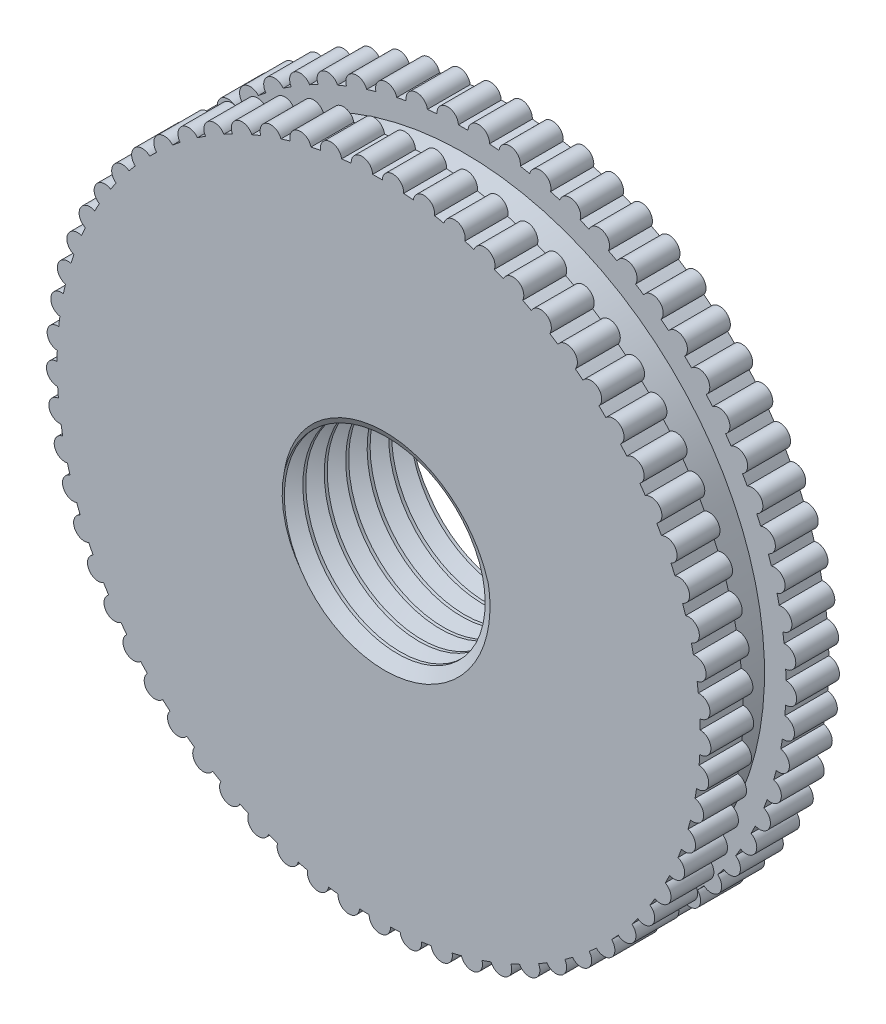
SolidWorks part; units mm, degrees
ref_plane "Front" through (0, 0, 0) normal (0, 0, 1) x (1, 0, 0)
ref_plane "Top" through (0, 0, 0) normal (0, 1, 0) x (1, 0, 0)
ref_plane "Right" through (0, 0, 0) normal (1, 0, 0) x (0, 0, -1)
sketch "Sketch1" plane through (0, 0, 0) normal (0, 0, 1) x (1, 0, 0)
  circle A0 centre (0, 0) radius 2.25
  circle A1 centre (0, 0) radius 7.5
  dimension "D1" = 4.5
  dimension "D2" = 15
extrude "Boss-Extrude1" add sketch "Sketch1" along normal blind 3
sketch "Sketch2" plane through (0, 0, 3) normal (0, 0, 1) x (1, 0, 0)
  circle A0 centre (0, 0) radius 2.25 construction
  circle A1 centre (0, 0) radius 2.25
curve "Helix/Spiral1" pitch 0.5 height 4.25 radius 2.25 centre (0, 0, 3) axis (0, 0, -1) start towards (1, 0, 0)
ref_plane "Plane1" through (2.25, 0, 3) normal (0, -0.9994, -0.0353) x (-1, 0, 0)
sketch "Sketch3" plane through (2.25, 0, 3) normal (0, -0.9994, -0.0353) x (-1, 0, 0)
  line L1 (-0.3732, 0.0174) -> (0.0425, -0.2226)
  line L2 (0.0425, -0.2226) -> (0.0425, 0.2574)
  line L3 (0.0425, 0.2574) -> (-0.3732, 0.0174)
  circle A0 centre (-0.096, 0.0174) radius 0.1386 construction
  point P1 (-0.096, 0.0174)
  dimension "D1" = 0.48
sweep "Cut-Sweep1" cut profiles "Sketch3" path "Helix/Spiral1" align with end faces yes
ref_plane "Plane2" through (0, 0, 0) normal (0, 0, -1) x (-1, 0, 0)
ref_plane "Plane3" through (0, 0, 1.5) normal (0, 0, -1) x (-1, 0, 0)
sketch "Sketch5" plane through (0, 0, 1.5) normal (0, 0, -1) x (-1, 0, 0)
  circle A0 centre (0, 0) radius 7.5 construction
  circle A1 centre (0, 0) radius 7.5
  circle A4 centre (0, 0) radius 7
  dimension "D1" = 0.5
extrude "Cut-Extrude1" cut sketch "Sketch5" against normal blind 0.5 and the other way blind 0.5
sketch "Sketch6" plane through (0, 0, 0) normal (0, 0, -1) x (-1, 0, 0)
  circle A0 centre (7.3977, 1.2348) radius 0.25
  circle A1 centre (0, 0) radius 7.5 construction
  circle A2 centre (7.4823, 0.5151) radius 0.25
  circle A3 centre (7.4971, -0.2095) radius 0.25
  circle A4 centre (7.4419, -0.9321) radius 0.25
  circle A5 centre (7.3172, -1.646) radius 0.25
  circle A6 centre (7.1241, -2.3445) radius 0.25
  circle A7 centre (6.8646, -3.0211) radius 0.25
  circle A8 centre (6.541, -3.6695) radius 0.25
  circle A9 centre (6.1563, -4.2837) radius 0.25
  circle A10 centre (5.7141, -4.8579) radius 0.25
  circle A11 centre (5.2186, -5.3867) radius 0.25
  circle A12 centre (4.6743, -5.8652) radius 0.25
  circle A13 centre (4.0864, -6.289) radius 0.25
  circle A14 centre (3.4604, -6.654) radius 0.25
  circle A15 centre (2.802, -6.9569) radius 0.25
  circle A16 centre (2.1175, -7.1949) radius 0.25
  circle A17 centre (1.4132, -7.3657) radius 0.25
  circle A18 centre (0.6957, -7.4677) radius 0.25
  circle A19 centre (-0.0283, -7.4999) radius 0.25
  circle A20 centre (-0.752, -7.4622) radius 0.25
  circle A21 centre (-1.4687, -7.3548) radius 0.25
  circle A22 centre (-2.1717, -7.1787) radius 0.25
  circle A23 centre (-2.8544, -6.9356) radius 0.25
  circle A24 centre (-3.5104, -6.6277) radius 0.25
  circle A25 centre (-4.1337, -6.258) radius 0.25
  circle A26 centre (-4.7184, -5.8298) radius 0.25
  circle A27 centre (-5.259, -5.3472) radius 0.25
  circle A28 centre (-5.7505, -4.8147) radius 0.25
  circle A29 centre (-6.1884, -4.2372) radius 0.25
  circle A30 centre (-6.5684, -3.6202) radius 0.25
  circle A31 centre (-6.8872, -2.9693) radius 0.25
  circle A32 centre (-7.1416, -2.2907) radius 0.25
  circle A33 centre (-7.3294, -1.5908) radius 0.25
  circle A34 centre (-7.4487, -0.876) radius 0.25
  circle A35 centre (-7.4984, -0.153) radius 0.25
  circle A36 centre (-7.4782, 0.5714) radius 0.25
  circle A37 centre (-7.3881, 1.2905) radius 0.25
  circle A38 centre (-7.2291, 1.9976) radius 0.25
  circle A39 centre (-7.0026, 2.6859) radius 0.25
  circle A40 centre (-6.7106, 3.3492) radius 0.25
  circle A41 centre (-6.3561, 3.9813) radius 0.25
  circle A42 centre (-5.9421, 4.5761) radius 0.25
  circle A43 centre (-5.4727, 5.1283) radius 0.25
  circle A44 centre (-4.9522, 5.6325) radius 0.25
  circle A45 centre (-4.3855, 6.0842) radius 0.25
  circle A46 centre (-3.7778, 6.4791) radius 0.25
  circle A47 centre (-3.1349, 6.8134) radius 0.25
  circle A48 centre (-2.4626, 7.0842) radius 0.25
  circle A49 centre (-1.7674, 7.2888) radius 0.25
  circle A50 centre (-1.0557, 7.4253) radius 0.25
  circle A51 centre (-0.3341, 7.4926) radius 0.25
  circle A52 centre (0.3906, 7.4898) radius 0.25
  circle A53 centre (1.1116, 7.4172) radius 0.25
  circle A54 centre (1.8223, 7.2752) radius 0.25
  circle A55 centre (2.5159, 7.0654) radius 0.25
  circle A56 centre (3.1861, 6.7896) radius 0.25
  circle A57 centre (3.8265, 6.4504) radius 0.25
  circle A58 centre (4.4312, 6.051) radius 0.25
  circle A59 centre (4.9945, 5.5951) radius 0.25
  circle A60 centre (5.5112, 5.0869) radius 0.25
  circle A61 centre (5.9764, 4.5312) radius 0.25
  circle A62 centre (6.3859, 3.9333) radius 0.25
  circle A63 centre (6.7357, 3.2986) radius 0.25
  circle A64 centre (7.0226, 2.6331) radius 0.25
  circle A65 centre (7.2439, 1.943) radius 0.25
  point P135 (0, 0)
  dimension "D1" = 0.5
  dimension "D2" = 65
extrude "Boss-Extrude3" add sketch "Sketch6" against normal blind 1
mirror "Mirror1" about plane through (0, 0, 1.5) normal (0, 0, -1) of "Boss-Extrude3"
